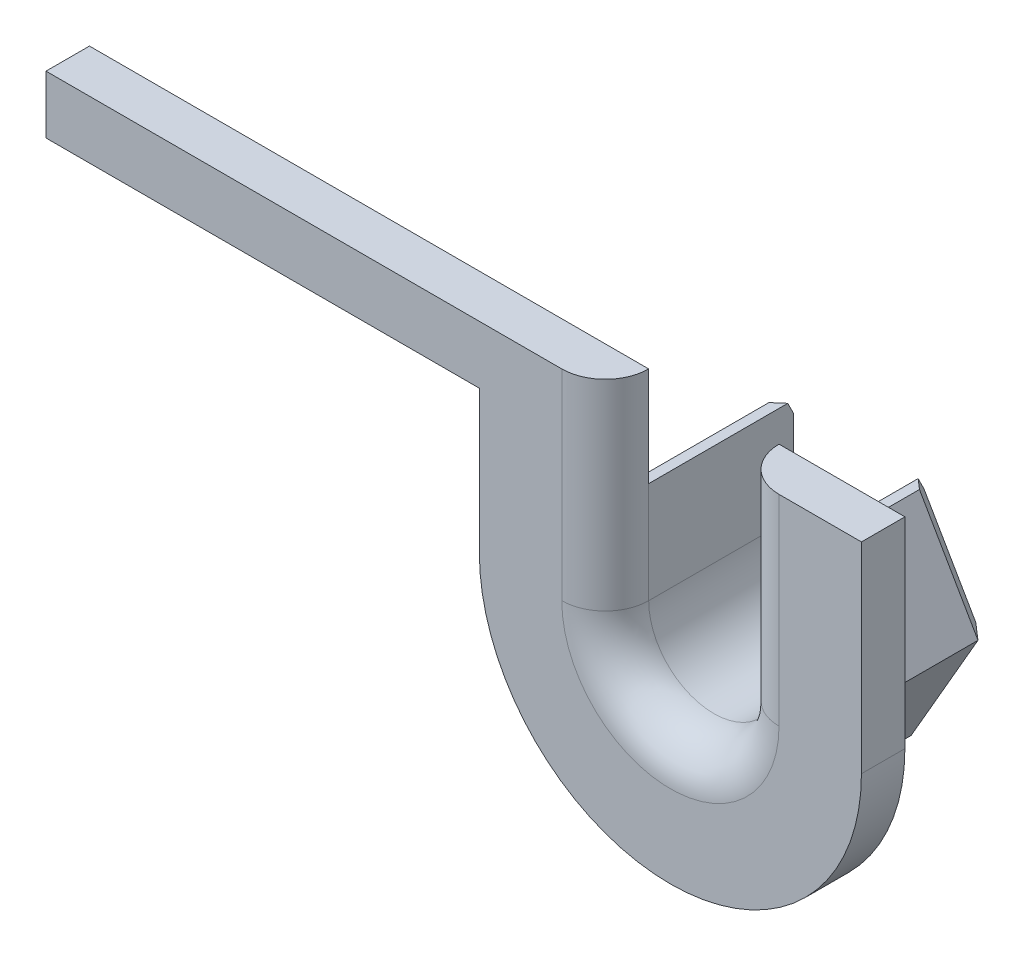
SolidWorks part; units mm, degrees
ref_plane "Front Plane" through (0, 0, 0) normal (0, 0, 1) x (1, 0, 0)
ref_plane "Top Plane" through (0, 0, 0) normal (0, 1, 0) x (1, 0, 0)
ref_plane "Right Plane" through (0, 0, 0) normal (1, 0, 0) x (0, 0, -1)
sketch "Sketch1" plane through (0, 0, 0) normal (0, 0, 1) x (1, 0, 0)
  line L0 (9.73, -24.18) -> (9.73, -20.18)
  line L1 (5.23, -24.18) -> (5.23, -20.18)
  line L12 (2.8612, -24.18) -> (5.1706, -28.18)
  line L13 (5.1706, -28.18) -> (9.7894, -28.18)
  line L14 (9.7894, -28.18) -> (12.0988, -24.18)
  line L15 (12.0988, -24.18) -> (9.7894, -20.18)
  line L16 (9.7894, -20.18) -> (5.1706, -20.18)
  line L17 (5.1706, -20.18) -> (2.8612, -24.18)
  line L18 (2.8612, -24.18) -> (5.1706, -28.18)
  line L19 (5.1706, -28.18) -> (9.7894, -28.18)
  line L20 (9.7894, -28.18) -> (12.0988, -24.18)
  line L21 (12.0988, -24.18) -> (9.7894, -20.18)
  line L22 (9.7894, -20.18) -> (5.1706, -20.18)
  line L23 (5.1706, -20.18) -> (2.8612, -24.18)
  line L32 (4.8819, -20.68) -> (10.0781, -20.68)
  circle A2 centre (7.48, -24.18) radius 2.25
  circle A3 centre (7.48, -24.18) radius 2.25
  dimension "D3" = 0.5
  dimension "D1" = 0.25
  dimension "D2" = 0.25
extrude "Boss-Extrude1" add sketch "Sketch1" against normal blind 5 contours A3 L19 L20 L21 L22 L23 L18 region at (9.849, -22.43, 0)
sketch "Sketch2" plane through (0, 0, 0) normal (0, 0, 1) x (1, 0, 0)
  line L0 (0.885, -19.25) -> (0.885, -18.7993)
  line L3 (5.23, -24.18) -> (5.23, -20.68) construction
  line L4 (9.73, -24.18) -> (9.73, -20.68) construction
  line L5 (5.23, -24.18) -> (5.23, -20.68)
  line L6 (9.73, -24.18) -> (9.73, -20.68)
  line L7 (-14.075, -19.25) -> (0.885, -19.25)
  line L8 (0.885, -19.25) -> (0.885, -24.18)
  line L9 (-14.075, -19.25) -> (0.885, -19.25)
  line L10 (14.075, -24.18) -> (14.075, -17.25)
  line L11 (14.075, -24.18) -> (14.075, -17.25)
  line L12 (14.075, -17.25) -> (10.575, -17.25)
  line L13 (14.075, -17.25) -> (10.575, -17.25)
  line L14 (10.575, -17.25) -> (-10.575, -17.25)
  line L15 (0.885, -19.25) -> (0.885, -24.18)
  line L16 (10.575, -17.25) -> (-10.575, -17.25)
  line L17 (-10.575, -17.25) -> (-14.075, -17.25)
  line L18 (-10.575, -17.25) -> (-14.075, -17.25)
  line L21 (9.73, -20.68) -> (9.73, -17.25)
  line L22 (5.23, -20.68) -> (5.23, -17.25)
  line L62 (-14.075, -17.25) -> (-14.075, -19.25)
  line L63 (-14.075, -17.25) -> (-14.075, -19.25)
  arc A0 (5.23, -24.18) -> (9.73, -24.18) centre (7.48, -24.18) ccw construction
  arc A1 (0.885, -24.18) -> (14.075, -24.18) centre (7.48, -24.18) ccw
  arc A2 (0.885, -24.18) -> (14.075, -24.18) centre (7.48, -24.18) ccw
  arc A3 (5.23, -24.18) -> (9.73, -24.18) centre (7.48, -24.18) ccw
  arc M9 (9.73, -24.18) -> (5.23, -24.18) centre (7.48, -24.18) cw
  line M11 (5.1706, -28.18) -> (9.7894, -28.18)
  line M12 (9.7894, -28.18) -> (12.0988, -24.18)
  line M13 (12.0988, -24.18) -> (10.0781, -20.68)
  line M15 (4.8819, -20.68) -> (2.8612, -24.18)
  line M16 (2.8612, -24.18) -> (5.1706, -28.18)
  line M17 (5.1706, -28.18) -> (9.7894, -28.18)
  dimension "D1" = 0
extrude "Boss-Extrude2" add sketch "Sketch2" along normal blind 1.5 contours L15 A2 L11 L13 L16 L0 M17 M16 M15 M13 M12 M11 | M9 M11 M12 M13 M15 M16 M17 region at (4.682, -22.8348, 0)
fillet "Fillet1" radius 1.5 3 edges at (9.73, -20.715, 1.5) (5.23, -20.715, 1.5) (7.48, -26.43, 1.5)
chamfer "Chamfer1" distance 0.5 angle 45 5 edges at (3.8716, -22.43, -5) (4.0159, -26.18, -5) (7.48, -28.18, -5) (10.9441, -26.18, -5) (11.0884, -22.43, -5)
